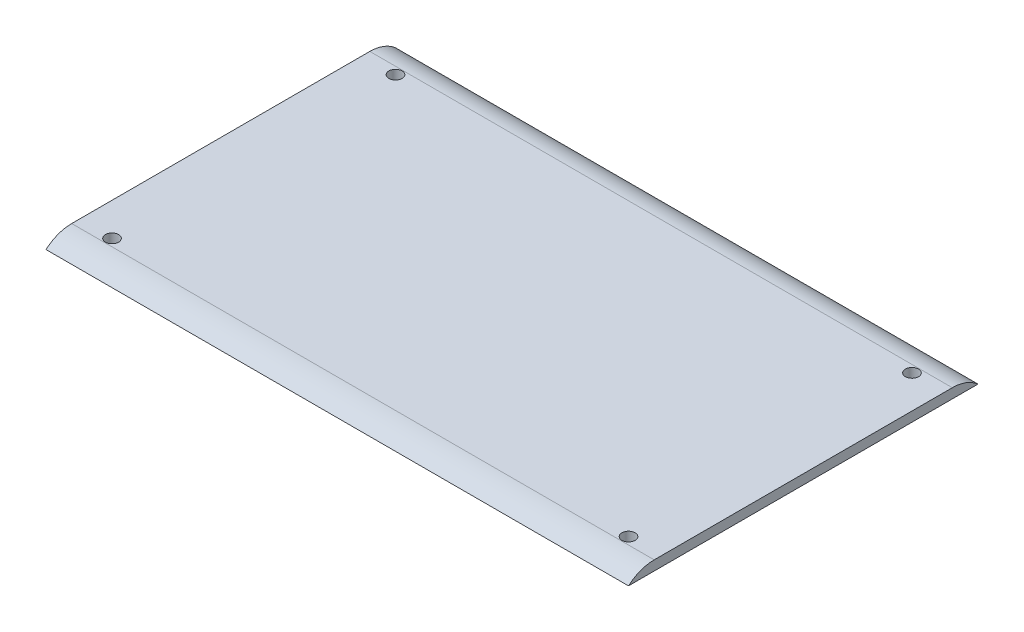
SolidWorks part; units mm, degrees
ref_plane "Front Plane" through (0, 0, 0) normal (0, 0, 1) x (1, 0, 0)
ref_plane "Top Plane" through (0, 0, 0) normal (0, 1, 0) x (1, 0, 0)
ref_plane "Right Plane" through (0, 0, 0) normal (1, 0, 0) x (0, 0, -1)
sketch "Sketch1" plane through (0, 0, 0) normal (0, 1, 0) x (1, 0, 0)
  line L1 (0, 0) -> (150, 0)
  line L2 (0, 0) -> (0, 90)
  line L3 (0, 90) -> (150, 90)
  line L4 (150, 0) -> (150, 90)
  dimension "D1" = 150
  dimension "D2" = 90
extrude "Boss-Extrude1" add sketch "Sketch1" along normal blind 2.5
fillet "Fillet1" radius 10 1 edges at (75, 2.5, 0)
fillet "Fillet2" radius 10 1 edges at (75, 2.5, -90)
sketch "Sketch2" plane through (0, 2.5, 0) normal (0, 1, 0) x (1, 0, 0)
  line L0 (0, 83.3856) -> (0, 6.6144) construction
  line L1 (150, 90) -> (0, 90) construction
  line L2 (0, 0) -> (150, 0) construction
  line L4 (150, 6.6144) -> (150, 83.3856) construction
  circle A0 centre (8.5, 81.5) radius 1.7
  circle A1 centre (8.5, 8.5) radius 1.7
  circle A2 centre (141.5, 81.5) radius 1.7
  circle A3 centre (141.5, 8.5) radius 1.7
  dimension "D1" = 3.4
  dimension "D2" = 8.5
  dimension "D3" = 8.5
  dimension "D4" = 3.4
  dimension "D5" = 8.5
  dimension "D6" = 8.5
  dimension "D7" = 3.4
  dimension "D8" = 8.5
  dimension "D9" = 8.5
  dimension "D10" = 3.4
  dimension "D11" = 8.5
  dimension "D12" = 8.5
extrude "Cut-Extrude1" cut sketch "Sketch2" against normal blind 2.5
